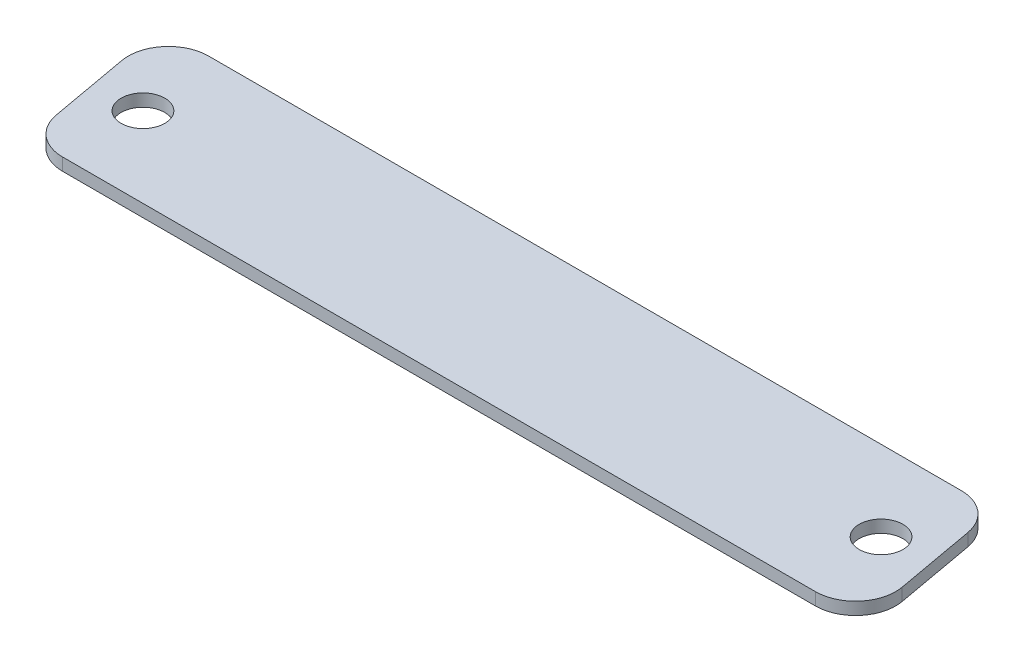
SolidWorks part; units mm, degrees
ref_plane "Front Plane" through (0, 0, 0) normal (0, 0, 1) x (1, 0, 0)
ref_plane "Top Plane" through (0, 0, 0) normal (0, 1, 0) x (1, 0, 0)
ref_plane "Right Plane" through (0, 0, 0) normal (1, 0, 0) x (0, 0, -1)
sketch "Sketch1" plane through (0, 0, 0) normal (0, 1, 0) x (1, 0, 0)
  line L3 (0, 0) -> (58.6486, 0)
  line L4 (0, 0) -> (0, 10.16)
  line L5 (0, 10.16) -> (58.6486, 10.16)
  line L6 (58.6486, 0) -> (58.6486, 10.16)
  dimension "D1" = 10.16
sheet metal parameters "Sheet-Metal1" thickness 0.7874 parameters "D1"=0.7366
base flange "Base-Flange1" sketch "Sketch1" thickness 0.7874 reverse thickness direction no parameters "D1"=0.7366
sketch "Sketch3" plane through (0, -0.7874, 0) normal (0, -1, 0) x (1, 0, 0)
  circle A0 centre (52.7933, -5.08) radius 1.9939 construction
  circle A1 centre (6.0508, -5.08) radius 1.9939 construction
  circle A2 centre (52.7933, -5.08) radius 1.9939 construction
  circle A3 centre (6.0508, -5.08) radius 1.9939 construction
  circle A4 centre (52.7933, -5.08) radius 1.3843
  circle A5 centre (6.0508, -5.08) radius 1.3843
  dimension "D1" = 2.7686
extrude "Cut-Extrude1" cut sketch "Sketch3" against normal through all normal cut yes
sketch "Sketch4" plane through (0, -0.7874, 0) normal (0, -1, 0) x (1, 0, 0)
  line L0 (60.7803, 22.2943) -> (49.9303, -37.8473) construction
  line L1 (-0.0796, -22.163) -> (8.4424, 25.0744) construction
  line L2 (60.7803, 22.2943) -> (49.9303, -37.8473) construction
  line L3 (-0.0796, -22.163) -> (8.4424, 25.0744) construction
  line L4 (54.9253, -10.16) -> (58.6486, -10.16)
  line L5 (58.6486, -10.16) -> (0, -10.16) construction
  line L6 (58.6486, -10.16) -> (58.6486, 0)
  line L7 (58.6486, 0) -> (56.7583, 0)
  line L8 (0, 0) -> (58.6486, 0) construction
  line L9 (56.7583, 0) -> (54.9253, -10.16)
  line L10 (2.0858, -10.16) -> (0, -10.16)
  line L11 (0, -10.16) -> (0, 0)
  line L12 (0, 0) -> (3.9188, 0)
  line L13 (2.0858, -10.16) -> (3.9188, 0)
extrude "Cut-Extrude2" cut sketch "Sketch4" against normal through all normal cut yes
fillet "Fillet1" radius 2.54 4 edges at (3.9188, -0.3937, 0) (2.0858, -0.3937, -10.16) (54.9253, -0.3937, -10.16) (56.7583, -0.3937, 0)
flat pattern "Flat-Pattern1" [suppressed]
sketch "Bend-Lines1" plane through (0, 0, 0) normal (0, 1, 0) x (1, 0, 0)
sketch3d "Bounding-Box1" [suppressed]
  line L0 (-59.6628, 15.8364, 0) -> (0, 15.8364, 0) construction
  line L1 (-59.6628, 0, 0) -> (0, 0, 0) construction
  line L2 (-59.6628, 15.8364, 0) -> (-59.6628, 0, 0) construction
  line L3 (0, 15.8364, 0) -> (0, 0, 0) construction
